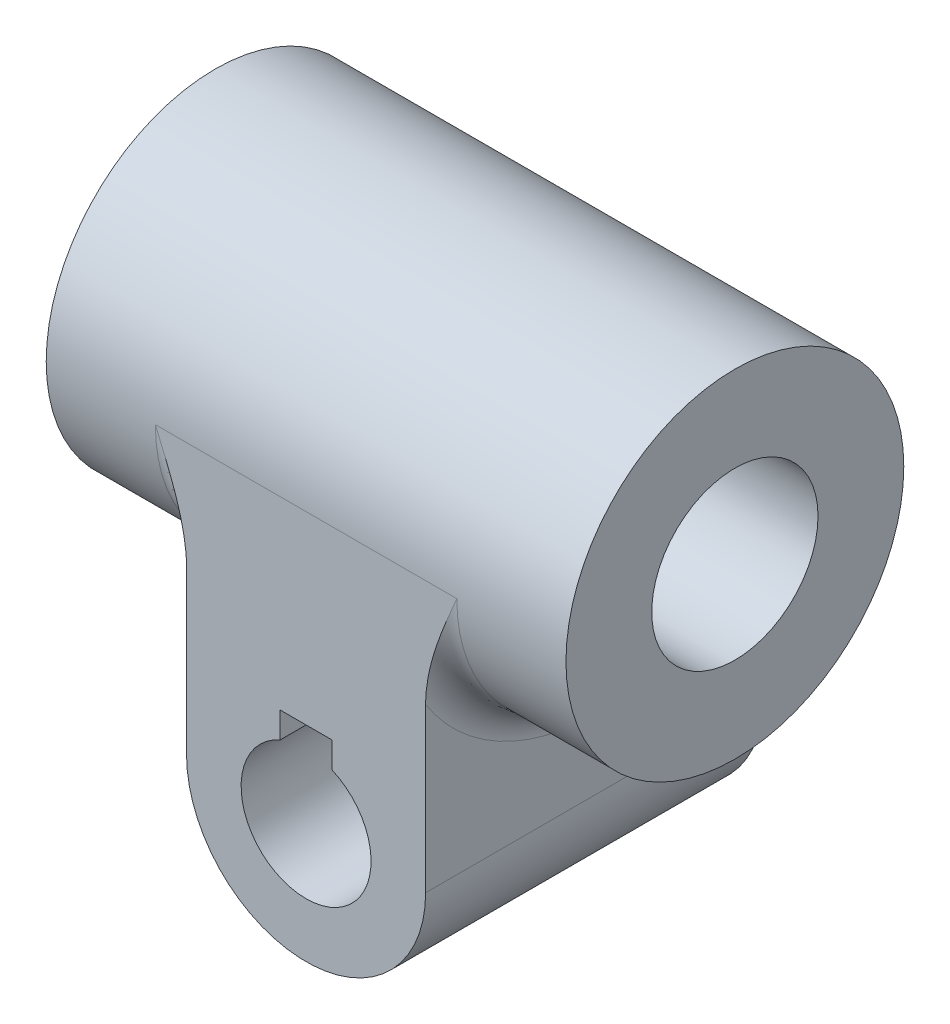
SolidWorks part; units mm, degrees
ref_plane "Front Plane" through (0, 0, 0) normal (0, 0, 1) x (1, 0, 0)
ref_plane "Top Plane" through (0, 0, 0) normal (0, 1, 0) x (1, 0, 0)
ref_plane "Right Plane" through (0, 0, 0) normal (1, 0, 0) x (0, 0, -1)
sketch "Sketch1" plane through (0, 0, 0) normal (1, 0, 0) x (0, 0, -1)
  line L0 (32.5, 0) -> (32.5, -75)
  line L1 (32.5, -75) -> (-32.5, -75)
  line L2 (-32.5, -75) -> (-32.5, 0)
  circle A0 centre (0, 0) radius 16
  circle A1 centre (0, 0) radius 32.5
  dimension "D1" = 65
  dimension "D2" = 32
  dimension "D3" = 75
extrude "Boss-Extrude1" add sketch "Sketch1" along normal mid plane 100 contours A1 A0 region at (0, -31.5808, 0)
extrude "Boss-Extrude2" add sketch "Sketch1<3>" along normal mid plane 46 contours A1 L2 L1 L0 region at (0, -49.7309, 0)
sketch "Sketch1<3>" plane through (0, 0, 0) normal (1, 0, 0) x (0, 0, -1) same geometry as "Sketch1"
sketch "Sketch2" plane through (0, 0, 32.5) normal (0, 0, 1) x (1, 0, 0)
  line L0 (5, -40.5436) -> (5, -35.5436)
  line L1 (5, -35.5436) -> (-5, -35.5436)
  line L2 (-5, -35.5436) -> (-5, -40.5436)
  line L3 (0, 5.1186) -> (0, -7.5741) construction
  line L6 (23, -75) -> (-23, -75) construction
  circle A0 centre (0, -52) radius 12.5
  circle A1 centre (0, -52) radius 23
  point P10 (6.2129, -41.1533)
  point P11 (-5.6574, -40.8536)
  line M7 (-23, 0) -> (-23, -75)
  line M8 (-23, -75) -> (23, -75)
  line M9 (23, -75) -> (23, 0)
  dimension "D1" = 5
  dimension "D2" = 25
  dimension "D3" = 46
  dimension "D4" = 10
extrude "Cut-Extrude1" cut sketch "Sketch2" against normal up to next contours A1 M8 M9 | A1 M7 M8 | A0 | A0 L0 L1 L2 region at (0, -37.7038, 32.5) region at (0, -52, 32.5) region at (17.8625, -69.8625, 32.5) region at (-17.8625, -69.8625, 32.5)
fillet "Fillet1" radius 6 2 edges at (-23, -32.5, 0) (23, -32.5, 0)
